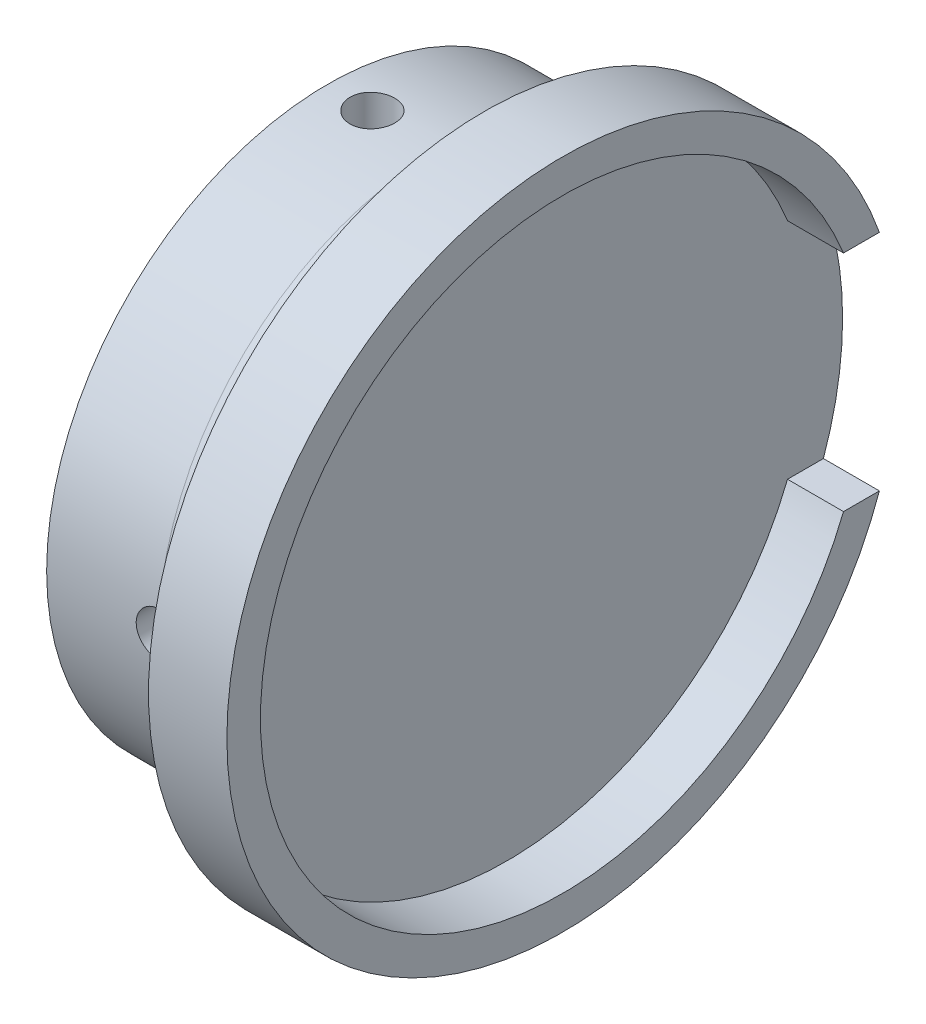
SolidWorks part; units mm, degrees
ref_plane "前视基准面" through (0, 0, 0) normal (0, 0, 1) x (1, 0, 0)
ref_plane "上视基准面" through (0, 0, 0) normal (0, 1, 0) x (1, 0, 0)
ref_plane "右视基准面" through (0, 0, 0) normal (1, 0, 0) x (0, 0, -1)
other "Configuration Table"
sketch "草图1" plane through (0, 0, 0) normal (1, 0, 0) x (0, 0, -1)
  circle A0 centre (0, 0) radius 12.55
  dimension "D1" = 25.1
extrude "凸台-拉伸1" add sketch "草图1" along normal blind 8
sketch "草图2" plane through (0, 0, 0) normal (-1, 0, 0) x (0, 0, 1)
  circle A0 centre (0, 0) radius 3
  dimension "D1" = 6
extrude "切除-拉伸1" cut sketch "草图2" against normal blind 7
sketch "草图3" plane through (0, 0, 0) normal (0, 1, 0) x (1, 0, 0)
  line L0 (0, 12.55) -> (0, -12.55) construction
  circle A0 centre (2, 0) radius 1
  dimension "D1" = 2
  dimension "D2" = 2
extrude "切除-拉伸2" cut sketch "草图3" against normal up to next and the other way up to next
sketch "草图4" plane through (0, 0, 0) normal (0, 0, 1) x (1, 0, 0)
  line L1 (0, 12.55) -> (0, -12.55) construction
  circle A0 centre (5, 0) radius 1
  dimension "D2" = 2
  dimension "D1" = 5
extrude "切除-拉伸3" cut sketch "草图4" against normal blind 19 and the other way blind 21
sketch "草图5" plane through (8, 0, 0) normal (1, 0, 0) x (0, 0, -1)
  circle A0 centre (0, 0) radius 15
  dimension "D1" = 30
extrude "凸台-拉伸2" add sketch "草图5" along normal blind 2.5 and the other way blind 1
sketch "草图6" plane through (10.5, 0, 0) normal (1, 0, 0) x (0, 0, -1)
  circle A0 centre (0, 0) radius 13.5
  dimension "D1" = 27
extrude "切除-拉伸4" cut sketch "草图6" against normal blind 2.5
fillet "圆角1" radius 2 1 edges at (7, 0, -12.55)
sketch "草图7" plane through (0, 0, 0) normal (0, 0, 1) x (1, 0, 0)
  line L0 (0, 0) -> (10.5, 0) construction
  line L7 (0, 12.55) -> (0, -12.55) construction
  line L8 (10.5, -15) -> (10.5, 15) construction
  line L10 (10.5, 5) -> (8, 5)
  line L11 (10.5, 5) -> (10.5, -5)
  line L12 (10.5, -5) -> (8, -5)
  line L13 (8, 5) -> (8, -5)
  dimension "D1" = 2.5
  dimension "D2" = 10
  dimension "D3" = 5
extrude "切除-拉伸5" cut sketch "草图7" against normal blind 21.5
